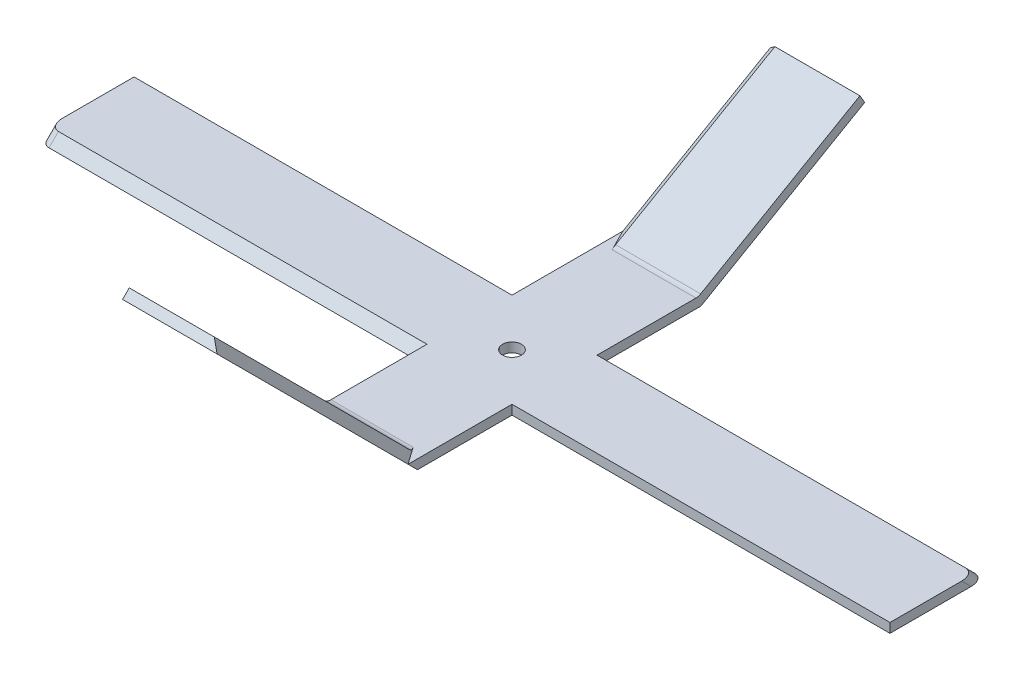
SolidWorks part; units mm, degrees
ref_plane "Front Plane" through (0, 0, 0) normal (0, 0, 1) x (1, 0, 0)
ref_plane "Top Plane" through (0, 0, 0) normal (0, 1, 0) x (1, 0, 0)
ref_plane "Right Plane" through (0, 0, 0) normal (1, 0, 0) x (0, 0, -1)
sketch "Sketch1" plane through (0, 0, 0) normal (1, 0, 0) x (0, 0, -1)
  line L0 (-14.2547, 0) -> (15.7453, 0)
  line L1 (15.7453, 0) -> (33.0658, 10)
  line L2 (-14.2547, 0) -> (-35.4679, 21.2132)
  line L3 (15.4774, 1) -> (32.5658, 10.866)
  line L4 (-13.8404, 1) -> (15.4774, 1)
  line L5 (-13.8404, 1) -> (-34.7608, 21.9203)
  line L6 (-35.4679, 21.2132) -> (-34.7608, 21.9203)
  line L7 (32.5658, 10.866) -> (33.0658, 10)
  dimension "D1" = 30
  dimension "D2" = 45
  dimension "D3" = 30
  dimension "D4" = 20
  dimension "D5" = 30
  dimension "D6" = 1
extrude "Top Blade First Extrude" add sketch "Sketch1" along normal blind 10
sketch "Sketch3" plane through (0, 0, 0) normal (0, -1, 0) x (1, 0, 0)
  line L0 (0, 14.2547) -> (10, -15.7453) construction
  line L1 (0, -15.7453) -> (10, 14.2547) construction
  line L2 (0, -5.7453) -> (-40, -5.7453)
  line L3 (0, 14.2547) -> (0, -15.7453) construction
  line L4 (-40, -5.7453) -> (-40, 4.2547)
  line L5 (-40, 4.2547) -> (0, 4.2547)
  line L6 (10, 4.2547) -> (50, 4.2547)
  line L7 (10, 14.2547) -> (10, -15.7453) construction
  line L8 (50, 4.2547) -> (50, -5.7453)
  line L9 (50, -5.7453) -> (10, -5.7453)
  line L10 (0, 4.2547) -> (0, -5.7453)
  line L11 (10, 4.2547) -> (10, -5.7453)
  dimension "D1" = 40
  dimension "D2" = 40
  dimension "D3" = 10
  dimension "D4" = 10
extrude "Top Blade Second Extrude" add sketch "Sketch3" against normal blind 1
chamfer "Top Blade Cut 1" distance 1 angle 45 4 edges at (0, 5.933, -24.0216) (10, 11.4602, 24.3006)
fillet "Top Blade Rounding 1" radius 1 2 edges at (50, 0.5, -5.2453) (-40, 0.5, 3.7547)
sketch "Sketch5" plane through (0, 0, 0) normal (0, -1, 0) x (1, 0, 0)
  line L0 (0, 4.2547) -> (10, -5.7453) construction
  line L1 (0, -5.7453) -> (10, 4.2547) construction
  circle A0 centre (5, -0.7453) radius 1
  dimension "D1" = 2
extrude "Top Blade Cut 2" cut sketch "Sketch5" against normal blind 19
fillet "Top Blade Rounding 2" radius 1 2 edges at (4.5, 1, 13.8404) (5.5, 1, -15.4774)
